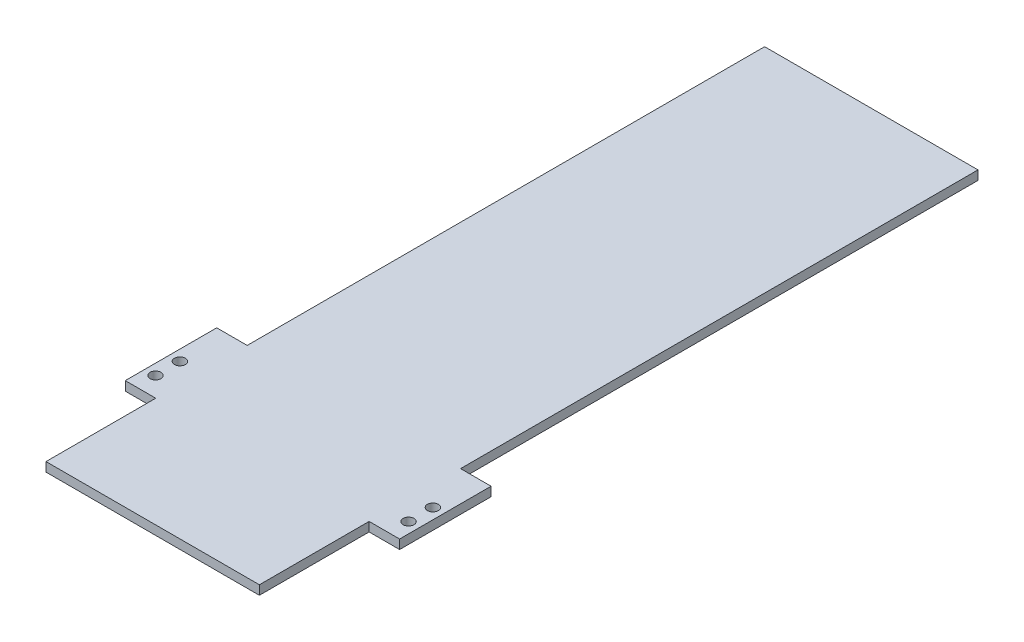
SolidWorks part; units mm, degrees
ref_plane "Front Plane" through (0, 0, 0) normal (0, 0, 1) x (1, 0, 0)
ref_plane "Top Plane" through (0, 0, 0) normal (0, 1, 0) x (1, 0, 0)
ref_plane "Right Plane" through (0, 0, 0) normal (1, 0, 0) x (0, 0, -1)
sketch "Sketch5" plane through (0, 0, 0) normal (0, 1, 0) x (1, 0, 0)
  line L0 (70, 36) -> (80, 36)
  line L1 (0, 0) -> (70, 0)
  line L2 (0, 0) -> (0, 235.74)
  line L3 (0, 235.74) -> (70, 235.74)
  line L4 (70, 0) -> (70, 235.74)
  line L5 (80, 36) -> (80, 66)
  line L6 (80, 66) -> (70, 66)
  line L7 (35, 235.74) -> (35, 0) construction
  line L8 (-10, 66) -> (0, 66)
  line L9 (-10, 36) -> (-10, 66)
  line L10 (0, 36) -> (-10, 36)
  dimension "D1" = 235.74
  dimension "D2" = 70
  dimension "D3" = 36
  dimension "D4" = 30
  dimension "D5" = 10
extrude "Boss-Extrude5" add sketch "Sketch5" along normal blind 3 contours L10 L2 L8 L9 | L7 L3 L2 L1 | L3 L7 L1 L4 | L5 L6 L4 L0 region at (75, 0, -51) region at (52.5, 0, -117.87) region at (17.5, 0, -117.87) region at (-5, 0, -51)
sketch "Sketch6" plane through (0, 3, 0) normal (0, 1, 0) x (1, 0, 0)
  point P0 (76.5, 50.4206)
  point P3 (76.5, 42.4206)
hole_wizard "M3 Clearance Hole1" positions "Sketch6" profile "Sketch7" hole size "M3" standard "ANSI Metric" end condition through all
sketch "Sketch7" plane through (76.5, 3, -50.4206) normal (1, 0, 0) x (0, 0, 1)
  line L0 (0, 0) -> (0, 3)
  line L1 (0, 3) -> (1.8, 3)
  line L2 (1.8, 3) -> (1.8, 0)
  line L5 (1.8, 0) -> (0, 0)
  line L11 (0, -6.35) -> (0, 107.95) construction
  dimension "Thru Hole Dia." = 3.6
  dimension "Thru Hole Depth" = 3
ref_plane "Plane1" through (35, 0, 0) normal (-1, 0, 0) x (0, 0, 1)
mirror "Mirror1" about plane through (35, 0, 0) normal (-1, 0, 0) of "M3 Clearance Hole1"
